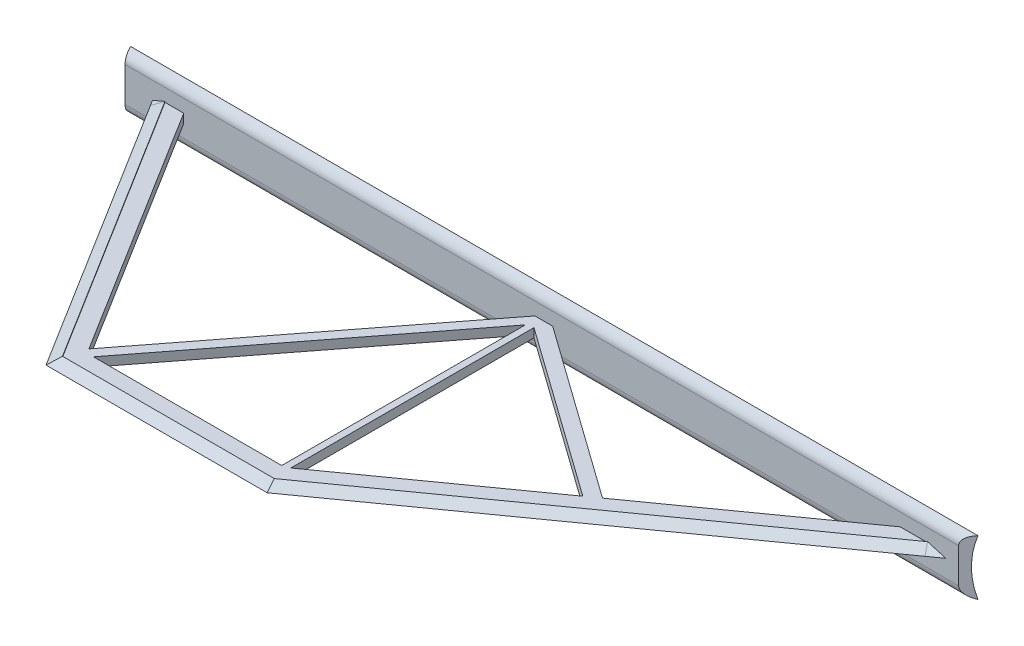
SolidWorks part; units mm, degrees
material "6061-T6 (SS)"
ref_plane "Front Plane" through (0, 0, 0) normal (0, 0, 1) x (1, 0, 0)
ref_plane "Top Plane" through (0, 0, 0) normal (0, 1, 0) x (1, 0, 0)
ref_plane "Right Plane" through (0, 0, 0) normal (1, 0, 0) x (0, 0, -1)
sketch "CS path" plane through (0, 0, 0) normal (0, 1, 0) x (1, 0, 0)
  line L0 (-228.6, 0) -> (228.6, 0) construction
  line L1 (-63.5, -163.068) -> (0, 0) construction
  line L2 (0, -163.068) -> (228.6, 0)
  line L3 (-228.6, 0) -> (-242.0318, 21.558) construction
  line L4 (228.6, 0) -> (290.6344, 44.2512) construction
  line L5 (228.6, 0) -> (290.6344, 44.2512)
  line L6 (-127, -163.068) -> (0, -163.068)
  line L8 (-228.6, 0) -> (-242.0318, 21.558)
  line L9 (-127, -163.068) -> (-228.6, 0) construction
  line L12 (-127, -163.068) -> (-228.6, 0)
  dimension "D1" = 163.068
  dimension "D2" = 127
  dimension "D3" = 457.2
  dimension "D4" = 228.6
  dimension "D5" = 0
  dimension "D6" = 25.4
  dimension "D7" = 76.2
sketch "Sketch8" plane through (0, 0, 0) normal (1, 0, 0) x (0, 0, -1)
  line L0 (0, 0) -> (82.804, 0) construction
  line L1 (82.804, 0) -> (-43.02, 26.7447) construction
  line L2 (82.804, 0) -> (-44.9942, -27.1644) construction
  line L3 (4.8299, 16.5739) -> (0, 17.6005)
  line L4 (4.8299, -16.5739) -> (0, -17.6005)
  line L5 (0, 17.6005) -> (0, -17.6005)
  line L6 (3.175, 0) -> (86.995, 0) construction
  arc A0 (4.8299, 16.5739) -> (4.8299, -16.5739) centre (86.995, 0) ccw
  dimension "D1" = 12
  dimension "D2" = 12
extrude "Boss-Extrude3" add sketch "Sketch8" along normal blind 254 and the other way blind 254 separate body
ref_plane "Plane7" through (0, 17.6005, 0) normal (0, -1, 0) x (1, 0, 0)
ref_plane "Plane8" through (290.6344, 0, -44.2512) normal (0.8141, 0, -0.5807) x (-0.5807, 0, -0.8141)
sketch "Sketch9" plane through (290.6344, 0, -44.2512) normal (0.8141, 0, -0.5807) x (-0.5807, 0, -0.8141)
  line L1 (0, 3.175) -> (9.525, 3.175)
  line L3 (0, -3.175) -> (9.525, -3.175)
  line L4 (9.525, 3.175) -> (9.525, -3.175)
  line L6 (0, 3.175) -> (-6.35, 0)
  line L7 (-6.35, 0) -> (0, -3.175)
  dimension "D3" = 9.525
sweep "Sweep2" add profiles "Sketch9" path "CS path"
sketch "Sketch11" plane through (-254, 0, 0) normal (-1, 0, 0) x (0, 0, 1)
  line L0 (-55.6299, -16.5739) -> (-55.6299, 16.5739)
  line L1 (-4.8299, 16.5739) -> (-55.6299, 16.5739)
  line L2 (-4.8299, -16.5739) -> (-55.6299, -16.5739)
  arc A0 (-4.8299, 16.5739) -> (-4.8299, -16.5739) centre (-86.995, 0) cw
  dimension "D1" = 50.8
extrude "Cut-Extrude1" cut sketch "Sketch11" against normal blind 762
sketch "Sketch12" plane through (0, 3.175, 0) normal (0, 1, 0) x (1, 0, 0)
  line L0 (-3.0491, -153.543) -> (-3.0491, 0) construction
  line L1 (-254, 0) -> (254, 0) construction
  line L2 (-3.0491, 0) -> (-121.7121, -153.543) construction
  line L3 (104.5745, -76.7715) -> (-3.0491, 0) construction
  line L4 (-6.8406, 0) -> (-123.4044, -150.8268)
  line L6 (-1.0491, -152.1163) -> (-1.0491, -6.3401)
  line L7 (-217.3775, 0) -> (-121.7121, -153.543)
  line L8 (-121.7121, -153.543) -> (-3.0491, -153.543)
  line L9 (-3.0491, -153.543) -> (212.1981, 0)
  line L10 (212.1981, 0) -> (-217.3775, 0)
  line L11 (-5.0491, -153.543) -> (-5.0491, -7.4939)
  line L12 (108.0185, -74.3148) -> (3.8388, 0)
  line L13 (101.1305, -79.2282) -> (-1.0491, -6.3401)
  line L14 (106.8974, -73.5151) -> (-0.7262, 3.2564) construction
  line L15 (-5.4229, 1.8345) -> (-124.0858, -151.7085) construction
  line L16 (-5.0491, -7.4939) -> (-117.9206, -153.543)
  line L18 (-1.0491, -153.543) -> (-1.0491, 0) construction
  line L19 (102.2516, -80.0279) -> (-5.372, -3.2564) construction
  line L21 (-5.0491, -153.543) -> (-5.0491, 0) construction
  line M9 (-121.7121, -153.543) -> (-217.3775, 0)
  dimension "D3" = 2
  dimension "D2" = 3
  dimension "D1" = 3
  dimension "D4" = 2
  dimension "D5" = 4
  dimension "D6" = 4
extrude "Boss-Extrude4" add sketch "Sketch12" against normal blind 6.35 contours L8 L9 L10 M9 region at (-1.5009, 3.175, 2.7773)
fillet "Fillet3" radius 6.35 2 edges at (0, -17.6005, 0) (0, 17.6005, 0)
ref_plane "Plane9" through (0, 16.5739, 0) normal (0, 1, 0) x (1, 0, 0)
sketch "Sketch13" plane through (0, 16.5739, 0) normal (0, 1, 0) x (1, 0, 0)
  line L0 (-254, 4.8299) -> (-254, 0)
  line L1 (254, 0) -> (-254, 0) construction
  line L2 (-254, 4.8299) -> (-254, 0) construction
  line L3 (-254, 0) -> (-252.5427, 0)
  line L4 (-252.5427, 0) -> (-254, 4.8299)
  line L5 (254, 4.8299) -> (254, 0)
  line L6 (254, 0) -> (247.2036, 0)
  line L7 (247.2036, 0) -> (254, 4.8299)
  line L9 (-130.5253, -169.418) -> (-233.9895, -3.3579) construction
  line L11 (-254, 4.8299) -> (254, 4.8299) construction
  dimension "D1" = 4.8299
  dimension "D2" = 73.21
  dimension "D3" = 54.6
  dimension "D4" = 58.075
extrude "Cut-Extrude2" cut sketch "Sketch13" against normal blind 50.8
sketch "Sketch14" plane through (0, 3.175, 0) normal (0, 1, 0) x (1, 0, 0)
  line L0 (228.6, 0) -> (-228.6, 0)
  line L1 (-228.6, 0) -> (-127, -163.068)
  line L2 (-127, -163.068) -> (0, -163.068)
  line L3 (0, -163.068) -> (228.6, 0)
extrude "Cut-Extrude3" cut sketch "Sketch14" against normal blind 0.508
mirror "Mirror1" about plane through (0, 0, 0) normal (0, 1, 0) of "Cut-Extrude3"
